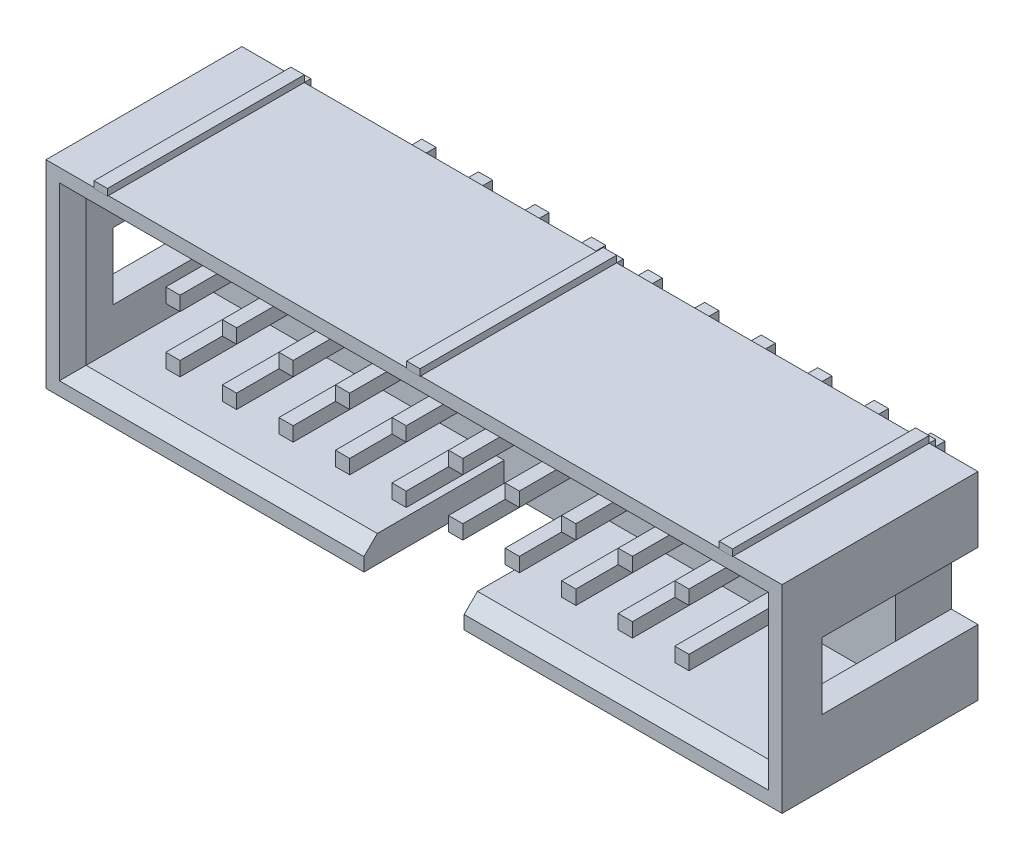
SolidWorks part; units mm, degrees
ref_plane "Front Plane" through (0, 0, 0) normal (0, 0, 1) x (1, 0, 0)
ref_plane "Top Plane" through (0, 0, 0) normal (0, 1, 0) x (1, 0, 0)
ref_plane "Right Plane" through (0, 0, 0) normal (1, 0, 0) x (0, 0, -1)
sketch "Эскиз1" plane through (0, 0, 0) normal (0, 0, 1) x (1, 0, 0)
  line L1 (0, 0) -> (33.06, 0)
  line L2 (0, 0) -> (0, 8.9)
  line L3 (0, 8.9) -> (33.06, 8.9)
  line L4 (33.06, 0) -> (33.06, 8.9)
  dimension "D1" = 33.06
  dimension "D2" = 8.9
extrude "Вытянуть1" add sketch "Эскиз1" along normal blind 8.8
sketch "Эскиз2" plane through (0, 0, 8.8) normal (0, 0, 1) x (1, 0, 0)
  line L0 (33.06, 8.9) -> (0, 8.9) construction
  line L1 (1.2, 7.7) -> (31.86, 7.7)
  line L2 (1.2, 7.7) -> (1.2, 1.2)
  line L3 (1.2, 1.2) -> (31.86, 1.2)
  line L4 (31.86, 7.7) -> (31.86, 1.2)
  line L5 (0, 0) -> (33.06, 0) construction
  line L6 (0, 8.9) -> (0, 0) construction
  line L7 (33.06, 0) -> (33.06, 8.9) construction
  dimension "D1" = 1.2
  dimension "D2" = 1.2
  dimension "D3" = 1.2
  dimension "D4" = 1.2
extrude "Вырез-Вытянуть1" cut sketch "Эскиз2" against normal blind 6.3
sketch "Эскиз7" plane through (33.06, 0, 0) normal (1, 0, 0) x (0, 0, -1)
  line L0 (0, 4.45) -> (-7.0578, 4.45) construction
  line L1 (0, 0) -> (0, 8.9) construction
  line L2 (-7, 2.95) -> (0, 2.95)
  line L3 (-7, 2.95) -> (-7, 5.95)
  line L4 (0, 2.95) -> (0, 5.95)
  line L5 (-7, 5.95) -> (0, 5.95)
  line L6 (-7, 2.95) -> (0, 5.95) construction
  line L7 (0, 2.95) -> (-7, 5.95) construction
  point P5 (-3.5, 4.45)
  dimension "D1" = 3
  dimension "D2" = 7
extrude "Вырез-Вытянуть2" cut sketch "Эскиз7" against normal up to surface (1.2 mm away) up to face at (31.86, 4.45, 5.65)
extrude "Вырез-Вытянуть5" cut sketch "Эскиз7<2>" along direction (-1, 0, 0) on the side of the normal up to surface (-31.86 mm away) from surface up to face at (1.2, 4.45, 5.65) starting at face at (0, 4.45, 4.4)
sketch "Эскиз7<2>" plane through (33.06, 0, 0) normal (1, 0, 0) x (0, 0, -1) same geometry as "Эскиз7"
sketch "Эскиз3" plane through (0, 0, 2.5) normal (0, 0, 1) x (1, 0, 0)
  line L0 (16.53, 7.7) -> (16.53, 1.2) construction
  line L1 (31.86, 7.7) -> (1.2, 7.7) construction
  line L2 (1.2, 1.2) -> (31.86, 1.2) construction
  line L3 (1.2, 4.45) -> (19.16, 4.45) construction
  line L4 (1.2, 7.7) -> (1.2, 1.2) construction
  line L6 (5.1, 8.9) -> (5.1, 0) construction
  line L7 (33.06, 8.9) -> (0, 8.9) construction
  line L8 (0, 0) -> (33.06, 0) construction
  line L9 (1.2, 5.72) -> (16.53, 5.72) construction
  line L10 (4.78, 6.04) -> (4.78, 5.4)
  line L11 (4.78, 6.04) -> (5.42, 6.04)
  line L12 (4.78, 5.4) -> (5.42, 5.4)
  line L13 (5.42, 6.04) -> (5.42, 5.4)
  line L14 (4.78, 6.04) -> (5.42, 5.4) construction
  line L15 (4.78, 5.4) -> (5.42, 6.04) construction
  line L16 (1.2, 7.7) -> (1.2, 5.95) construction
  point P21 (5.1, 5.72)
  dimension "D4" = 3.9
  dimension "D1" = 0.64
  dimension "D2" = 1.27
  dimension "D3" = 15.33
extrude "Вытянуть2" add sketch "Эскиз3" along normal blind 5.7 and the other way blind 5.8
sketch "Эскиз4" plane through (0, 0, 0) normal (0, -1, 0) x (1, 0, 0)
  line L0 (16.53, 8.8) -> (16.53, 0) construction
  line L1 (0, 8.8) -> (33.06, 8.8) construction
  line L2 (0, 0) -> (33.06, 0) construction
  line L3 (14.28, 2.5) -> (14.28, 8.8)
  line L4 (14.28, 2.5) -> (18.78, 2.5)
  line L5 (14.28, 8.8) -> (18.78, 8.8)
  line L6 (18.78, 2.5) -> (18.78, 8.8)
  line L7 (14.28, 2.5) -> (18.78, 8.8) construction
  line L8 (14.28, 8.8) -> (18.78, 2.5) construction
  point P7 (16.53, 5.65)
  dimension "D1" = 4.5
  dimension "D2" = 3.15
extrude "Вытянуть3" cut sketch "Эскиз4" against normal up to next
sketch "Эскиз5" plane through (0, 0, 0) normal (0, 0, -1) x (-1, 0, 0)
  line L0 (-16.53, 8.9) -> (-16.53, 0) construction
  line L1 (-33.06, 8.9) -> (0, 8.9) construction
  line L2 (0, 0) -> (-33.06, 0) construction
  line L3 (-16.23, 8.9) -> (-16.83, 8.9)
  line L4 (-16.83, 8.9) -> (-16.83, 0)
  line L5 (-16.83, 0) -> (-16.23, 0)
  line L6 (-16.23, 8.9) -> (-16.23, 0)
  line L7 (-30.26, 8.9) -> (-30.86, 8.9)
  line L8 (-30.86, 8.9) -> (-30.86, 0)
  line L9 (-30.56, 8.9) -> (-30.56, 0) construction
  line L10 (-30.26, 8.9) -> (-30.26, 0)
  line L11 (-30.86, 0) -> (-30.26, 0)
  line L12 (-33.06, 0) -> (-33.06, 2.95) construction
  line L13 (-2.5, 8.9) -> (-2.5, 0) construction
  line L14 (-2.2, 0) -> (-2.8, 0)
  line L15 (-2.8, 8.9) -> (-2.8, 0)
  line L16 (-2.2, 8.9) -> (-2.2, 0)
  line L17 (-2.8, 8.9) -> (-2.2, 8.9)
  dimension "D1" = 0.3
  dimension "D2" = 2.5
  dimension "D3" = 0.3
extrude "Вытянуть4" add sketch "Эскиз5" along normal blind 0.3
sketch "Эскиз6" plane through (0, 8.9, 0) normal (0, 1, 0) x (1, 0, 0)
  line L0 (30.86, 0) -> (30.26, 0)
  line L1 (30.86, 0) -> (30.86, -8.8246)
  line L2 (30.26, 0) -> (30.26, -8.8246)
  line L3 (30.86, -8.8246) -> (30.26, -8.8246)
  line L4 (16.83, 0) -> (16.23, 0)
  line L5 (16.83, 0) -> (16.83, -8.8329)
  line L6 (16.23, 0) -> (16.23, -8.8329)
  line L7 (16.83, -8.8329) -> (16.23, -8.8329)
  line L8 (2.8, 0) -> (2.2, 0)
  line L9 (2.8, 0) -> (2.8, -8.8417)
  line L10 (2.2, 0) -> (2.2, -8.8417)
  line L11 (2.8, -8.8417) -> (2.2, -8.8417)
extrude "Вытянуть5" add sketch "Эскиз6" along normal blind 0.3
chamfer "Фаска1" distance 0.6 angle 45 5 edges at (25.32, 1.2, 8.8) (31.86, 4.45, 8.8) (7.74, 1.2, 8.8) (1.2, 4.45, 8.8) (16.53, 7.7, 8.8)
pattern_linear "Линейный массив1" count 10 spacing 2.54 along (1, 0, 0) count 2 spacing 2.54 along (0, -1, 0) of "Вытянуть2"
